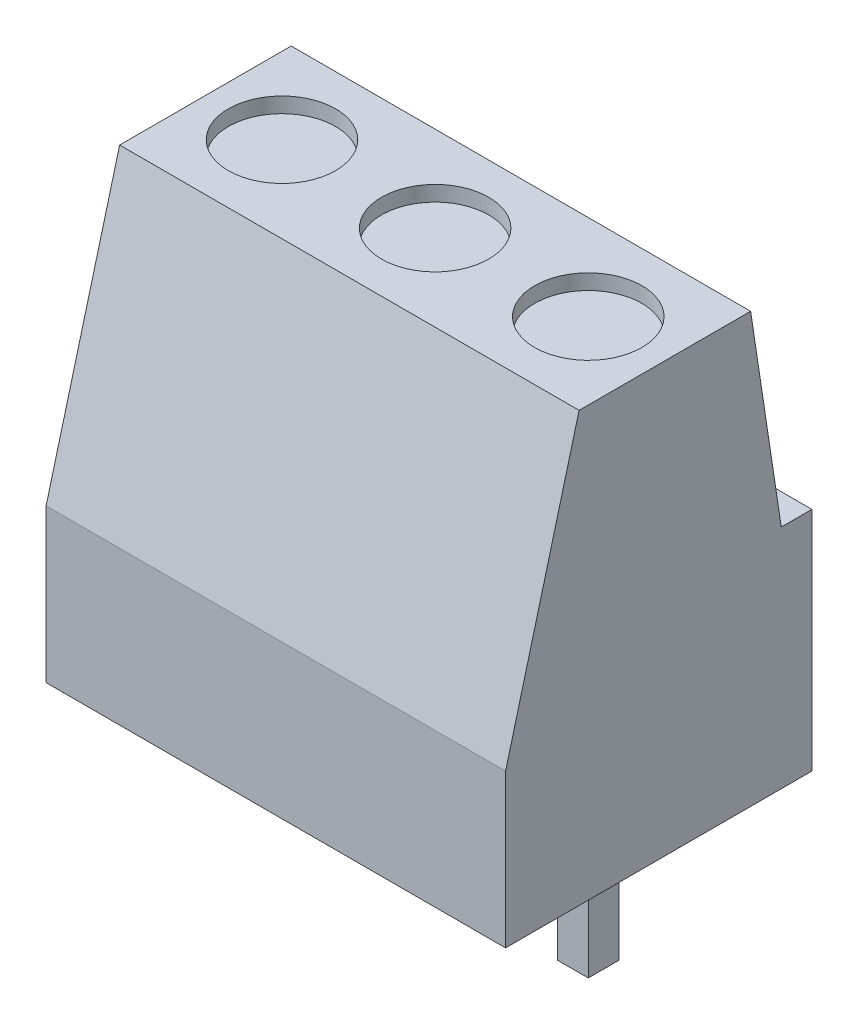
SolidWorks part; units mm, degrees
ref_plane "Front Plane" through (0, 0, 0) normal (0, 0, 1) x (1, 0, 0)
ref_plane "Top Plane" through (0, 0, 0) normal (0, 1, 0) x (1, 0, 0)
ref_plane "Right Plane" through (0, 0, 0) normal (1, 0, 0) x (0, 0, -1)
sketch "Sketch3" plane through (0, 0, 0) normal (0, 1, 0) x (1, 0, 0)
  line L0 (0, -5) -> (0, 5) construction
  line L1 (-7.5, 5) -> (7.5, 5)
  line L2 (-7.5, 5) -> (-7.5, -5)
  line L3 (-7.5, -5) -> (7.5, -5)
  line L4 (7.5, 5) -> (7.5, -5)
  line L9 (7.5, 0) -> (-7.5, 0) construction
  point P8 (0, 0)
  dimension "D1" = 10
  dimension "D2" = 15
extrude "Boss-Extrude3" add sketch "Sketch3" along normal blind 14 separate body
sketch "Sketch4" plane through (-7.5, 0, 0) normal (-1, 0, 0) x (0, 0, 1)
  line L2 (-4, 7.4) -> (-3, 14)
  line L3 (-3, 14) -> (-5, 14)
  line L6 (5, 14) -> (2.6, 14)
  line L7 (2.6, 14) -> (5, 5)
  line L10 (-3, 14) -> (2.6, 14) construction
  line L12 (5, 14) -> (5, 0) construction
  line L13 (5, 5) -> (5, 14)
  line L14 (-5, 14) -> (5, 14) construction
  line L16 (-4, 7.4) -> (-5, 7.4)
  line L17 (-5, 14) -> (-5, 0) construction
  line L18 (-5, 7.4) -> (-5, 14)
  line L20 (-5, 0) -> (5, 0) construction
  dimension "D1" = 7.4
  dimension "D2" = 2.4
  dimension "D3" = 2
  dimension "D4" = 5
  dimension "D5" = 1
extrude "Cut-Extrude1" cut sketch "Sketch4" against normal through all
sketch "Sketch5" plane through (0, 14, 0) normal (0, 1, 0) x (1, 0, 0)
  line L0 (-7.5, 0.2) -> (7.5, 0.2) construction
  line L1 (-7.5, 3) -> (-7.5, -2.6) construction
  line L2 (7.5, -2.6) -> (7.5, 3) construction
  circle A2 centre (-5, 0.2) radius 1.75
  dimension "D3" = 3.5
  dimension "D1" = 5
extrude "Cut-Extrude2" cut sketch "Sketch5" against normal blind 0.5
sketch "Sketch6" plane through (0, 0, -5) normal (0, 0, -1) x (-1, 0, 0)
  line L0 (-7.5, 0) -> (7.5, 0) construction
  line L1 (3.5, 4.4) -> (6.5, 4.4)
  line L2 (3.5, 4.4) -> (3.5, 1.4)
  line L3 (3.5, 1.4) -> (6.5, 1.4)
  line L4 (6.5, 4.4) -> (6.5, 1.4)
  point P6 (5, 1.4)
  dimension "D1" = 3
  dimension "D2" = 3
  dimension "D3" = 1.4
  dimension "D4" = 5
extrude "Cut-Extrude4" cut sketch "Sketch6" against normal blind 0.5
pattern_linear "LPattern2" count 3 spacing 5 along (1, 0, 0) of "Cut-Extrude2", "Cut-Extrude4"
sketch "Sketch7" plane through (0, 0, 0) normal (0, -1, 0) x (1, 0, 0)
  line L0 (-7.5, 0) -> (7.5, 0) construction
  line L1 (-7.5, -5) -> (-7.5, 5) construction
  line L2 (7.5, 5) -> (7.5, -5) construction
  line L4 (-5.46, -0.5) -> (-4.46, -0.5)
  line L5 (-5.46, -0.5) -> (-5.46, 0.5)
  line L6 (-5.46, 0.5) -> (-4.46, 0.5)
  line L7 (-4.46, -0.5) -> (-4.46, 0.5)
  line L8 (-5.46, -0.5) -> (-4.46, 0.5) construction
  line L9 (-5.46, 0.5) -> (-4.46, -0.5) construction
  point P6 (-4.96, 0)
  dimension "D1" = 1
  dimension "D2" = 2.54
extrude "Boss-Extrude4" add sketch "Sketch7" along normal blind 4 separate body
pattern_linear "LPattern3" count 3 spacing 5.08 along (1, 0, 0) of "Boss-Extrude4"
ref_axis "Axis1" through (-4.96, 0, 0) along (0, -1, 0)
